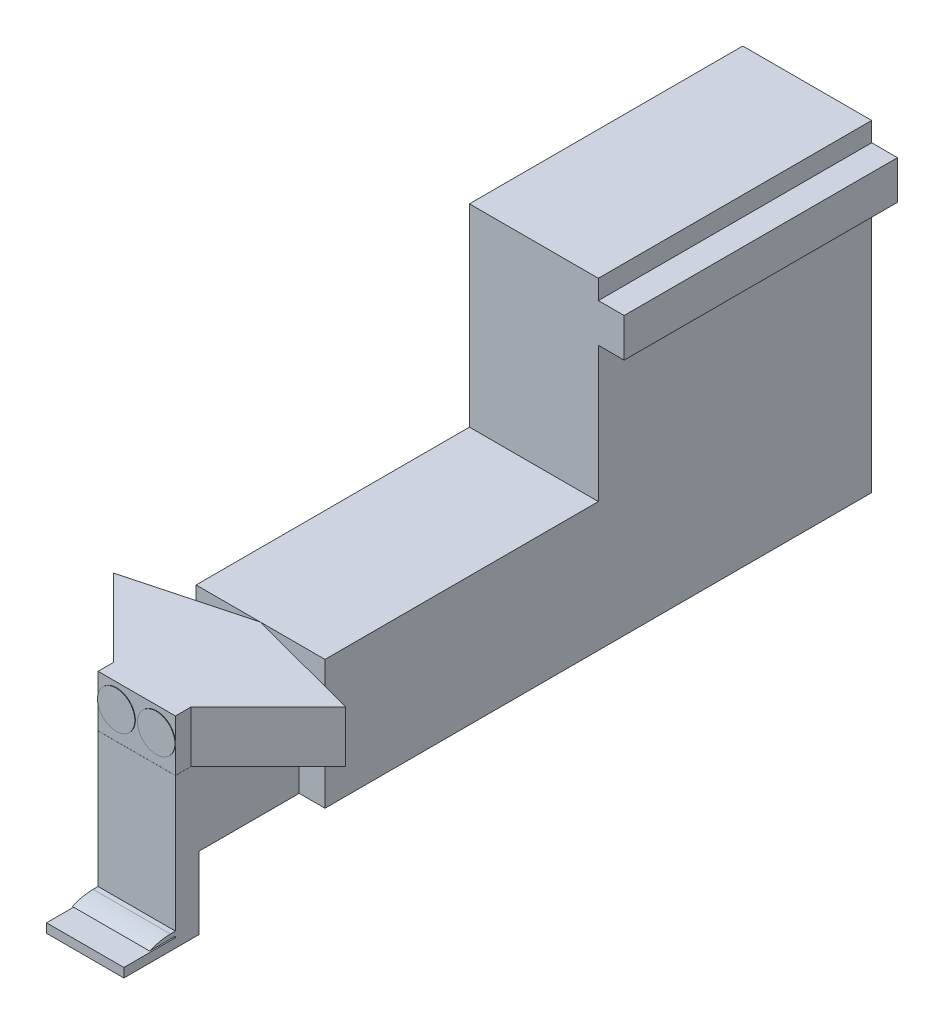
SolidWorks part; units mm, degrees
ref_plane "Front Plane" through (0, 0, 0) normal (0, 0, 1) x (1, 0, 0)
ref_plane "Top Plane" through (0, 0, 0) normal (0, 1, 0) x (1, 0, 0)
ref_plane "Right Plane" through (0, 0, 0) normal (1, 0, 0) x (0, 0, -1)
sketch "Sketch2" plane through (0, 0, 0) normal (0, 0, 1) x (1, 0, 0)
  line L0 (0, -3.75) -> (0, 3.75) construction
  line L1 (5, 3.75) -> (0, 3.75)
  line L2 (5, 3.75) -> (5, -3.75)
  line L3 (5, -3.75) -> (0, -3.75)
  line L4 (0, 3.75) -> (0, -3.75) construction
  line L5 (5, 3.75) -> (0, -3.75) construction
  line L6 (5, -3.75) -> (0, 3.75) construction
  line L7 (-25, -55) -> (0, -55)
  line L8 (-25, -55) -> (-25, 7.5)
  line L9 (-25, 7.5) -> (0, 7.5)
  line L10 (0, -55) -> (0, -3.75)
  line L11 (-25, -55) -> (0, 7.5) construction
  line L12 (-25, 7.5) -> (0, -55) construction
  line L13 (0, 3.75) -> (0, 7.5)
  point P0 (2.5, 0)
  point P8 (-12.5, -23.75)
  dimension "D1" = 7.5
  dimension "D2" = 5
  dimension "D3" = 25
  dimension "D4" = 7.5
  dimension "D5" = 55
extrude "Boss-Extrude1" add sketch "Sketch2" along normal mid plane 53
sketch "Sketch3" plane through (0, 0, 26.5) normal (0, 0, 1) x (1, 0, 0)
  line L0 (-25, -55) -> (0, -55) construction
  line L1 (-25, -55) -> (0, -55)
  line L2 (-25, -30) -> (0, -30)
  line L3 (-25, 7.5) -> (-25, -55) construction
  line L4 (0, -55) -> (0, -3.75) construction
  line L5 (0, -30) -> (0, -55)
  line L6 (-25, -30) -> (-25, -55)
  dimension "D1" = 25
extrude "Boss-Extrude2" add sketch "Sketch3" along normal blind 53
sketch "Sketch4" plane through (0, -30, 0) normal (0, 1, 0) x (1, 0, 0)
  line L0 (-12.5, -79.5) -> (-35, -85.5)
  line L1 (0, -79.5) -> (-25, -79.5) construction
  line L2 (-12.5, -79.5) -> (10, -85.5)
  line L3 (-35, -85.5) -> (-20, -100.5)
  line L4 (10, -85.5) -> (-5, -100.5)
  line L6 (-20, -100.5) -> (-5, -100.5) construction
  line L7 (-20, -100.5) -> (-20, -103.5)
  line L8 (-20, -103.5) -> (-5, -103.5)
  line L9 (-5, -100.5) -> (-5, -103.5)
  point P4 (0, 0)
  dimension "D1" = 45
  dimension "D2" = 6
  dimension "D3" = 45
  dimension "D4" = 15
  dimension "D5" = 3
extrude "Boss-Extrude3" add sketch "Sketch4" against normal blind 10 separate body
sketch "Sketch6" plane through (0, -55, 0) normal (0, -1, 0) x (1, 0, 0)
  line L0 (-25, 79.5) -> (0, 79.5) construction
  line L1 (-20, 79.5) -> (-5, 79.5)
  line L2 (-20, 79.5) -> (-20, 103.5)
  line L3 (-20, 103.5) -> (-5, 103.5)
  line L4 (-5, 79.5) -> (-5, 103.5)
  line L5 (-20, 100.5) -> (-20, 103.5) construction
  point P7 (0, 0)
extrude "Boss-Extrude9" add sketch "Sketch6" against normal blind 14.99
sketch "Sketch8" plane through (-5, 0, 0) normal (1, 0, 0) x (0, 0, -1)
  line L0 (-103.5, -66.13) -> (-103.5, -66.98) construction
  line L1 (-103.5, -55) -> (-98.9, -55)
  line L2 (-103.5, -55) -> (-103.5, -66.13)
  line L3 (-103.5, -69) -> (-98.9, -69)
  line L4 (-98.9, -55) -> (-98.9, -69)
  line L5 (-103.5, -69) -> (-113.5, -69)
  line L6 (-103.5, -69) -> (-103.5, -67.23) construction
  line L7 (-103.5, -67.23) -> (-113.5, -67.23)
  line L8 (-113.5, -69) -> (-113.5, -67.23)
  line L9 (-103.5, -66.98) -> (-108.5, -66.98)
  line L10 (-103.5, -66.98) -> (-103.5, -66.13) construction
  line L11 (-103.5, -66.13) -> (-108.5, -66.13)
  line L12 (-108.5, -66.98) -> (-108.5, -66.13)
  line L13 (-103.5, -66.98) -> (-103.5, -67.23)
  line L14 (-103.5, -67.23) -> (-103.5, -69) construction
  dimension "D1" = 14
  dimension "D2" = 4.6
  dimension "D3" = 10
  dimension "D4" = 1.77
  dimension "D5" = 0.25
  dimension "D6" = 5
  dimension "D7" = 0.85
extrude "Boss-Extrude10" add sketch "Sketch8" against normal up to surface (15 mm away) up to face at (-20, -47.505, 91.5)
fillet "Fillet1" radius 10 1 edges at (-12.5, -66.13, 108.5)
sketch "Sketch9" plane through (0, 0, 103.5) normal (0, 0, 1) x (1, 0, 0)
  line L0 (-20, -40) -> (-20, -30) construction
  line L1 (-20, -40) -> (-20, -30) construction
  line L2 (-5, -40) -> (-5, -30) construction
  circle A0 centre (-16.398, -34.5922) radius 3.625
  circle A1 centre (-8.625, -34.5922) radius 3.625
  point P2 (-20, -35)
  point P7 (0, 0)
  dimension "D1" = 7.25
extrude "Boss-Extrude11" add sketch "Sketch9" along normal blind 0.1
